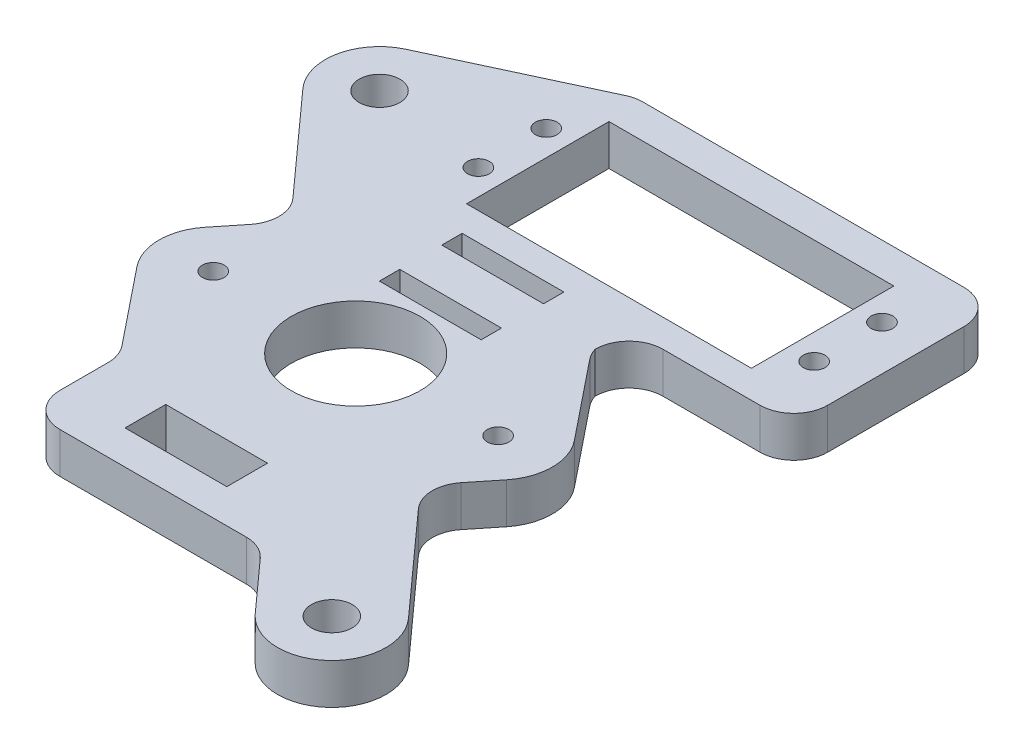
SolidWorks part; units mm, degrees
material "MDF"
ref_plane "Plano frontal" through (0, 0, 0) normal (0, 0, 1) x (1, 0, 0)
ref_plane "Plano superior" through (0, 0, 0) normal (0, 1, 0) x (1, 0, 0)
ref_plane "Plano direito" through (0, 0, 0) normal (1, 0, 0) x (0, 0, -1)
ref_plane "Plano1" through (0, -6, 0) normal (0, -1, 0) x (1, 0, 0)
sketch "Esboço1" plane through (0, -6, 0) normal (0, -1, 0) x (1, 0, 0)
  line L0 (30.7936, -136.5537) -> (52.8946, -146.8291)
  line L1 (55.0026, -147.2952) -> (102.3526, -147.2952)
  line L2 (107.3526, -142.2952) -> (107.3526, -122.2)
  line L3 (102.3526, -117.2) -> (88.05, -117.2)
  line L4 (83.05, -112.2) -> (83.05, -88.8837)
  line L5 (84.3343, -85.538) -> (103.6789, -64.0537)
  line L6 (91.7885, -53.3476) -> (85.0372, -60.8457)
  line L7 (81.3215, -62.5) -> (53.85, -62.5)
  line L8 (48.85, -67.5) -> (48.85, -99.1163)
  line L9 (47.5657, -102.462) -> (28.2211, -123.9463)
  line L10 (73.45, -114.2) -> (73.45, -117.2)
  line L11 (73.45, -117.2) -> (58.45, -117.2)
  line L12 (58.45, -117.2) -> (58.45, -114.2)
  line L13 (58.45, -114.2) -> (73.45, -114.2)
  line L14 (58.45, -108) -> (58.45, -105)
  line L15 (58.45, -105) -> (73.45, -105)
  line L16 (73.45, -105) -> (73.45, -108)
  line L17 (73.45, -108) -> (58.45, -108)
  line L18 (58.45, -67.5) -> (73.45, -67.5)
  line L19 (73.45, -67.5) -> (73.45, -73.5)
  line L20 (73.45, -73.5) -> (58.45, -73.5)
  line L21 (58.45, -73.5) -> (58.45, -67.5)
  line L22 (55.0026, -142.2952) -> (55.0026, -121.2952)
  line L23 (55.0026, -121.2952) -> (97.0026, -121.2952)
  line L24 (97.0026, -121.2952) -> (97.0026, -142.2952)
  line L25 (97.0026, -142.2952) -> (55.0026, -142.2952)
  line L26 (34.1663, -129.2994) -> (97.7337, -58.7006) construction
  line L27 (44.95, -94) -> (86.95, -94) construction
  line L28 (44.3524, -106.0308) -> (38.7129, -99.0099)
  line L29 (38.7129, -88.9901) -> (48.85, -76.3698)
  line L30 (83.05, -111.6302) -> (93.1871, -99.0099)
  line L31 (93.1871, -88.9901) -> (87.5476, -81.9692)
  arc A0 (52.8946, -146.8291) -> (55.0026, -147.2952) centre (55.0026, -142.2952) ccw
  arc A1 (102.3526, -147.2952) -> (107.3526, -142.2952) centre (102.3526, -142.2952) ccw
  arc A2 (107.3526, -122.2) -> (102.3526, -117.2) centre (102.3526, -122.2) ccw
  arc A3 (88.05, -117.2) -> (83.05, -112.2) centre (88.05, -112.2) cw
  arc A4 (83.05, -88.8837) -> (84.3343, -85.538) centre (88.05, -88.8837) cw
  arc A5 (103.6789, -64.0537) -> (91.7885, -53.3476) centre (97.7337, -58.7006) ccw
  arc A6 (85.0372, -60.8457) -> (81.3215, -62.5) centre (81.3215, -57.5) cw
  arc A7 (53.85, -62.5) -> (48.85, -67.5) centre (53.85, -67.5) ccw
  arc A8 (48.85, -99.1163) -> (47.5657, -102.462) centre (43.85, -99.1163) cw
  arc A9 (28.2211, -123.9463) -> (30.7936, -136.5537) centre (34.1663, -129.2994) ccw
  circle A10 centre (65.95, -94) radius 9.5
  circle A11 centre (44.95, -94) radius 1.6
  circle A12 centre (86.95, -94) radius 1.6
  arc A13 (38.7129, -99.0099) -> (38.7129, -88.9901) centre (44.95, -94) cw
  arc A14 (93.1871, -99.0099) -> (93.1871, -88.9901) centre (86.95, -94) ccw
  circle A15 centre (100.7526, -126.7952) radius 1.6
  circle A16 centre (100.7526, -136.7952) radius 1.6
  circle A17 centre (51.2526, -126.7952) radius 1.6
  circle A18 centre (51.2526, -136.7952) radius 1.6
  circle A19 centre (34.1663, -129.2994) radius 3
  circle A20 centre (97.7337, -58.7006) radius 3
  point P37 (65.95, -105)
  point P41 (65.95, -94)
  point P68 (36.95, -94)
  point P74 (94.95, -94)
  dimension "D16" = 3.2
  dimension "D20" = 6
  dimension "D25" = 5
  dimension "D27" = 19
  dimension "D1" = 42
  dimension "D2" = 21
  dimension "D3" = 10
  dimension "D4" = 49.5
  dimension "D5" = 95
  dimension "D6" = 3
  dimension "D7" = 15
  dimension "D8" = 34.2
  dimension "D9" = 6
  dimension "D10" = 14.6974
  dimension "D11" = 32.7952
  dimension "D12" = 40.7
  dimension "D13" = 6.2
  dimension "D14" = 5
  dimension "D15" = 5
  dimension "D17" = 5.5
  dimension "D18" = 3.75
  dimension "D19" = 48
  dimension "D21" = 8
  dimension "D22" = 9.6
  dimension "D23" = 6.6
  dimension "D24" = 4.0952
  dimension "D26" = 11
  dimension "D28" = 42
  dimension "D29" = 8
  dimension "D30" = 30
  dimension "D31" = 30
extrude "Ressalto-extrusão1" add sketch "Esboço1" against normal blind 6 contours L9 A9 L0 A0 L1 A1 L2 A2 L3 A3 L4 A4 L5 A5 L6 A6 L7 A7 L8 A8 A19 A17 A15 L12 L13 L10 L11 L16 L17 L14 L15 L20 L21 L18 L19 L24 L25 L22 L23 | L30 A14 L31 L5 A4 L4 A12 | A13 L28 L9 A8 L8 L29 A11 region at (68.7945, -6, -103.5655) region at (44.0199, -6, -92.593) region at (87.8801, -6, -95.407)
fillet "Filete1" radius 5 4 edges at (83.05, -3, -111.6302) (87.5476, -3, -81.9692) (48.85, -3, -76.3698) (44.3524, -3, -106.0308)
